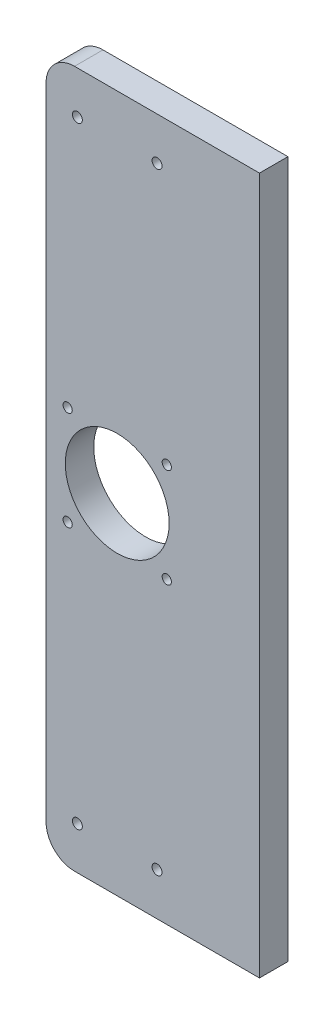
SolidWorks part; units mm, degrees
material "Органическое стекло СО-95-К ГОСТ 10667-90"
ref_plane "Спереди" through (0, 0, 0) normal (0, 0, 1) x (1, 0, 0)
ref_plane "Сверху" through (0, 0, 0) normal (0, 1, 0) x (1, 0, 0)
ref_plane "Справа" through (0, 0, 0) normal (1, 0, 0) x (0, 0, -1)
ref_axis "ОсьX" through (-88.99, 0, 0) along (1, 0, 0)
ref_axis "ОсьZ" through (0, 55, 0) along (0, -1, 0)
ref_axis "ОсьY" through (0, 0, -88.99) along (0, 0, 1)
sketch "Эскиз1" plane through (0, 0, 0) normal (0, 0, 1) x (1, 0, 0)
  line L0 (0, 0) -> (0, 59.9562) construction
  line L1 (-50, 245) -> (100, 245)
  line L2 (-50, 245) -> (-50, -245)
  line L3 (-50, -245) -> (100, -245)
  line L4 (100, 245) -> (100, -245)
  line L5 (-34.85, 34.85) -> (0, 0) construction
  line L6 (-50, 245) -> (-50, -245)
  line L7 (100, 245) -> (100, -245)
  line L8 (-109.4093, 0) -> (189.9089, 0) construction
  circle A0 centre (-28, 215) radius 3.5
  circle A16 centre (28, 215) radius 3.5
  circle A17 centre (28, -215) radius 3.5
  circle A18 centre (-28, -215) radius 3.5
  circle A19 centre (0, 0) radius 36.5
  circle A24 centre (0, 0) radius 49.2853 construction
  circle A25 centre (-34.85, 34.85) radius 3.25
  circle A26 centre (34.85, 34.85) radius 3.25
  circle A27 centre (34.85, -34.85) radius 3.25
  circle A28 centre (-34.85, -34.85) radius 3.25
  point P6 (-50, 0)
  dimension "D3" = 7
  dimension "D4" = 430
  dimension "D5" = 56
  dimension "D6" = 73
  dimension "D8" = 45
  dimension "D9" = 69.7
  dimension "D10" = 6.5
  dimension "D11" = 98.5707
  dimension "D1" = 150
  dimension "D2" = 490
  dimension "D7" = 100
extrude "Бобышка-Вытянуть1" add sketch "Эскиз1" along normal blind 20 contours L4 L1 L2 L3 A18 A16 A0 region at (25, 239.8755, 0)
fillet "Скругление2" radius 20 2 edges at (-50, -245, 10) (-50, 245, 10)
